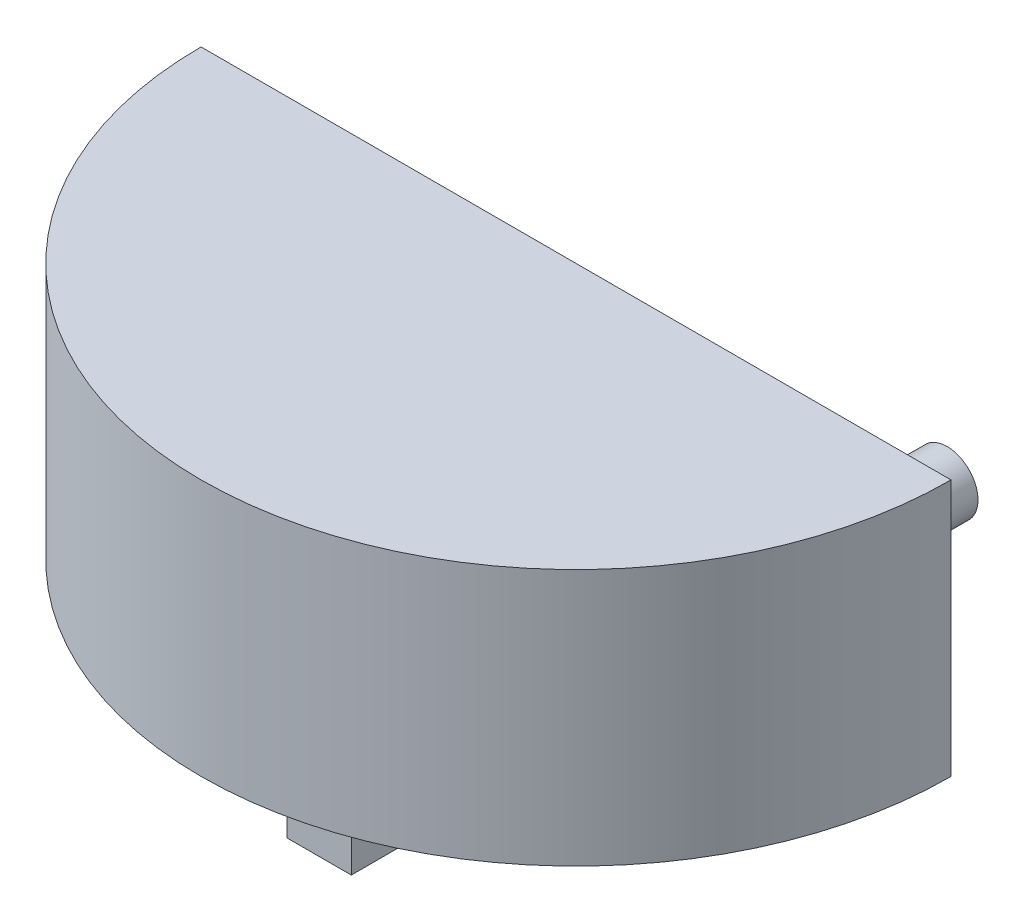
SolidWorks part; units mm, degrees
ref_plane "Front Plane" through (0, 0, 0) normal (0, 0, 1) x (1, 0, 0)
ref_plane "Top Plane" through (0, 0, 0) normal (0, 1, 0) x (1, 0, 0)
ref_plane "Right Plane" through (0, 0, 0) normal (1, 0, 0) x (0, 0, -1)
sketch "Sketch1" plane through (0, 0, 0) normal (0, 0, 1) x (1, 0, 0)
  line L0 (0, 0) -> (9.271, 0)
  line L2 (9.271, 0) -> (0, 0)
  line L3 (9.271, 0) -> (9.271, 6.35)
  line L4 (9.271, 6.35) -> (0, 6.35)
  line L5 (0, 0) -> (0, 6.35)
  line L6 (-7.6835, 1.5875) -> (7.6835, 1.5875)
  line L7 (-7.6835, 1.5875) -> (-7.6835, 4.7625)
  line L8 (-7.6835, 4.7625) -> (7.6835, 4.7625)
  line L9 (7.6835, 1.5875) -> (7.6835, 4.7625)
  line L10 (-7.6835, 1.5875) -> (7.6835, 4.7625) construction
  line L11 (-7.6835, 4.7625) -> (7.6835, 1.5875) construction
  point P5 (0, 3.175)
  dimension "D1" = 9.271
  dimension "D2" = 6.35
  dimension "D3" = 3.175
  dimension "D4" = 1.5875
revolve "Revolve1" add sketch "Sketch1" angle 360 about L5 region at (0.1124, 0.7937, 0)
sketch "Sketch2" plane through (0, 6.35, 0) normal (0, 1, 0) x (1, 0, 0)
  line L0 (-9.271, 0) -> (9.271, 0)
  line L2 (-9.271, 0) -> (10.0432, 0)
  line L3 (-9.271, 0) -> (-9.271, 10.1441)
  line L4 (-9.271, 10.1441) -> (10.0432, 10.1441)
  line L5 (10.0432, 0) -> (10.0432, 10.1441)
  circle A0 centre (0, 0) radius 9.271 construction
  circle M2 centre (0, 0) radius 9.271
extrude "Cut-Extrude1" cut sketch "Sketch2" against normal blind 9.398 contours L2 L5 L4 L3 M2 | L0 M2 region at (0, 6.35, -3.9347) region at (-9.0528, 6.35, -5.072)
sketch "Sketch3" plane through (0, 0, 0) normal (0, -1, 0) x (1, 0, 0)
  line L0 (9.271, 0) -> (-9.271, 0) construction
  circle A0 centre (5.3022, 0) radius 1.1906
  circle A1 centre (-5.3022, 0) radius 1.1906
  dimension "D1" = 2.3813
  dimension "D2" = 2.3813
  dimension "D3" = 3.9688
  dimension "D4" = 3.9688
extrude "Cut-Extrude2" cut sketch "Sketch3" against normal blind 3.048
sketch "Sketch4" plane through (0, 0, 0) normal (0, 0, -1) x (-1, 0, 0)
  line L0 (-9.271, 6.35) -> (-9.271, 0) construction
  line L1 (9.271, 6.35) -> (-9.271, 6.35) construction
  line L2 (-9.271, 0) -> (-6.4929, 0) construction
  line L3 (9.271, 0) -> (9.271, 6.35) construction
  circle A0 centre (-8.382, 5.461) radius 0.762
  circle A4 centre (-8.382, 0.889) radius 0.8255
  circle A5 centre (8.382, 5.461) radius 0.8255
  circle A6 centre (8.382, 0.889) radius 0.762
  dimension "D1" = 1.524
  dimension "D5" = 1.651
  dimension "D6" = 1.651
  dimension "D2" = 0.889
  dimension "D3" = 0.889
  dimension "D4" = 0.889
  dimension "D7" = 0.889
  dimension "D8" = 0.889
extrude "Boss-Extrude1" add sketch "Sketch4" along normal blind 0.7937
sketch "Sketch6" plane through (0, 0, -0.7937) normal (0, 0, -1) x (-1, 0, 0)
  circle A0 centre (-8.382, 0.889) radius 0.8255
  circle A1 centre (8.382, 5.461) radius 0.8255
extrude "Cut-Extrude3" cut sketch "Sketch6" against normal blind 1.5875
sketch "Sketch7" plane through (0, 0, 0) normal (0, -1, 0) x (1, 0, 0)
  line L0 (-0.7938, 0) -> (0.7937, 0)
  line L1 (0.7937, -6.35) -> (-0.7938, -6.35)
  line L2 (0.7937, -6.35) -> (0.7937, 6.35)
  line L3 (0.7937, 6.35) -> (-0.7938, 6.35)
  line L4 (-0.7938, -6.35) -> (-0.7938, 6.35)
  line L5 (0.7937, -6.35) -> (-0.7938, 6.35) construction
  line L6 (0.7937, 6.35) -> (-0.7938, -6.35) construction
  point P0 (0, 0)
  line M8 (-4.1116, 0) -> (4.1116, 0)
  dimension "D1" = 1.5875
  dimension "D2" = 12.7
extrude "Boss-Extrude2" add sketch "Sketch7" along normal blind 3.175 contours L4 L2 L3 M8 region at (0, 0, 3.175)
